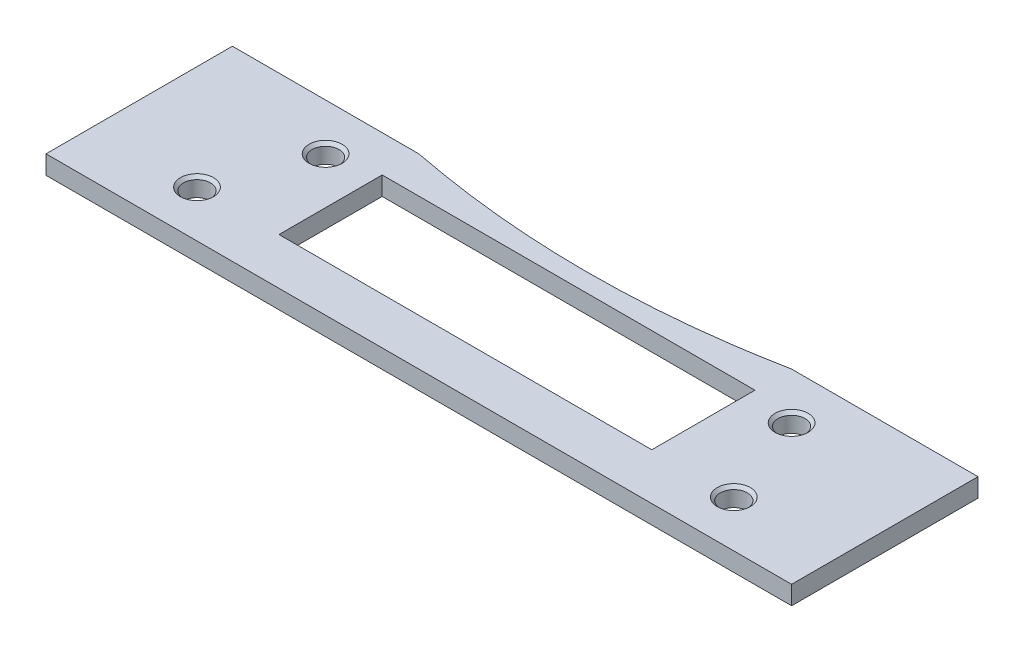
SolidWorks part; units mm, degrees
ref_plane "前视基准面" through (0, 0, 0) normal (0, 0, 1) x (1, 0, 0)
ref_plane "上视基准面" through (0, 0, 0) normal (0, 1, 0) x (1, 0, 0)
ref_plane "右视基准面" through (0, 0, 0) normal (1, 0, 0) x (0, 0, -1)
other "Configuration Table"
sketch "草图1" plane through (0, 0, 0) normal (0, 1, 0) x (1, 0, 0)
  line L0 (0, 0) -> (80, 0)
  line L2 (0, 0) -> (0, 20)
  line L3 (0, 20) -> (80, 20)
  line L4 (80, 0) -> (80, 20)
  dimension "D1" = 80
  dimension "D2" = 20
extrude "凸台-拉伸1" add sketch "草图1" along normal blind 2 contours L3 L4 L0 L2
sketch "草图2" plane through (0, 2, 0) normal (0, 1, 0) x (1, 0, 0)
  line L0 (11.2, 5) -> (68.8, 5) construction
  line L2 (40, 16.0706) -> (10.7614, 16.0706) construction
  line L3 (0, 0) -> (80, 0) construction
  line L4 (40, 16.0706) -> (67.7357, 16.0706) construction
  line L5 (0, 0) -> (0, 20) construction
  line L6 (20, 16.0706) -> (60, 16.0706)
  line L7 (20, 16.0706) -> (20, 5)
  line L8 (0, 0) -> (0, 20) construction
  line L9 (0, 20) -> (80, 20) construction
  line L10 (80, 0) -> (80, 20) construction
  line L11 (20, 5) -> (60, 5)
  line L13 (60, 16.0706) -> (60, 5)
  circle A0 centre (15, 15) radius 1
  circle A1 centre (65, 15) radius 1
  circle A2 centre (11.2, 5) radius 1
  circle A3 centre (68.8, 5) radius 1
  point P10 (15, 15)
  point P11 (65, 15)
  point P17 (11.2, 5)
  point P18 (68.8, 5)
  dimension "D2" = 5
  dimension "D4" = 15
  dimension "D1" = 2
  dimension "D10" = 2
  dimension "D11" = 2
  dimension "D3" = 2
  dimension "D5" = 5
  dimension "D6" = 15
  dimension "D7" = 5
  dimension "D8" = 11.2
  dimension "D9" = 5
  dimension "D12" = 11.2
  dimension "D13" = 50
  dimension "D14" = 57.6
  dimension "D15" = 20
  dimension "D16" = 11.0706
  dimension "D17" = 5
  dimension "D18" = 20
sketch "草图4" plane through (0, 2, 0) normal (0, 1, 0) x (1, 0, 0)
  point P0 (15, 15)
  point P3 (11.2, 5)
  point P6 (65, 15)
  point P9 (68.8, 5)
hole_wizard "M3.5 螺纹孔1" positions "草图4" profile "草图5" tap size "M3.5" standard "GB" end condition through all
sketch "草图5" plane through (15, 2, -15) normal (1, 0, 0) x (0, 0, 1)
  line L0 (0, 0) -> (0, 2)
  line L1 (0, 2) -> (1.45, 2)
  line L2 (1.45, 2) -> (1.45, 0.325)
  line L3 (1.45, 0.325) -> (1.775, 0)
  line L5 (1.775, 0) -> (0, 0)
  line L6 (-1.45, 0.325) -> (-1.775, 0) construction
  line L11 (0, -6.35) -> (0, 107.95) construction
  dimension "通孔螺纹孔钻头直径" = 2.9
  dimension "通孔螺纹孔钻头深度" = 2
  dimension "近端锥形沉头孔直径" = 3.55
  dimension "近端锥形沉头孔角度" = 90
cosmetic thread "孔螺蚊线1" parameters "D2"=3.5
cosmetic thread "孔螺蚊线2" parameters "D2"=3.5
cosmetic thread "孔螺蚊线3" parameters "D2"=3.5
cosmetic thread "孔螺蚊线4" parameters "D2"=3.5
extrude "切除-拉伸2" cut sketch "草图2" against normal blind 10
sketch "草图7" plane through (0, 2, 0) normal (0, 1, 0) x (1, 0, 0)
  line L0 (20, 16.0706) -> (20, 20) construction
  line L1 (0, 20) -> (80, 20) construction
  line L2 (60, 16.0706) -> (60, 20) construction
  line L4 (60, 20) -> (20, 20)
  line L5 (40, 16.0706) -> (40, 20) construction
  line L6 (60, 16.0706) -> (20, 16.0706) construction
  spline S1 degree 2 poles (20, 20) (40, 16.0706) (60, 20) knots 0 0 0 1 1 1
extrude "切除-拉伸5" cut sketch "草图7" against normal blind 10
